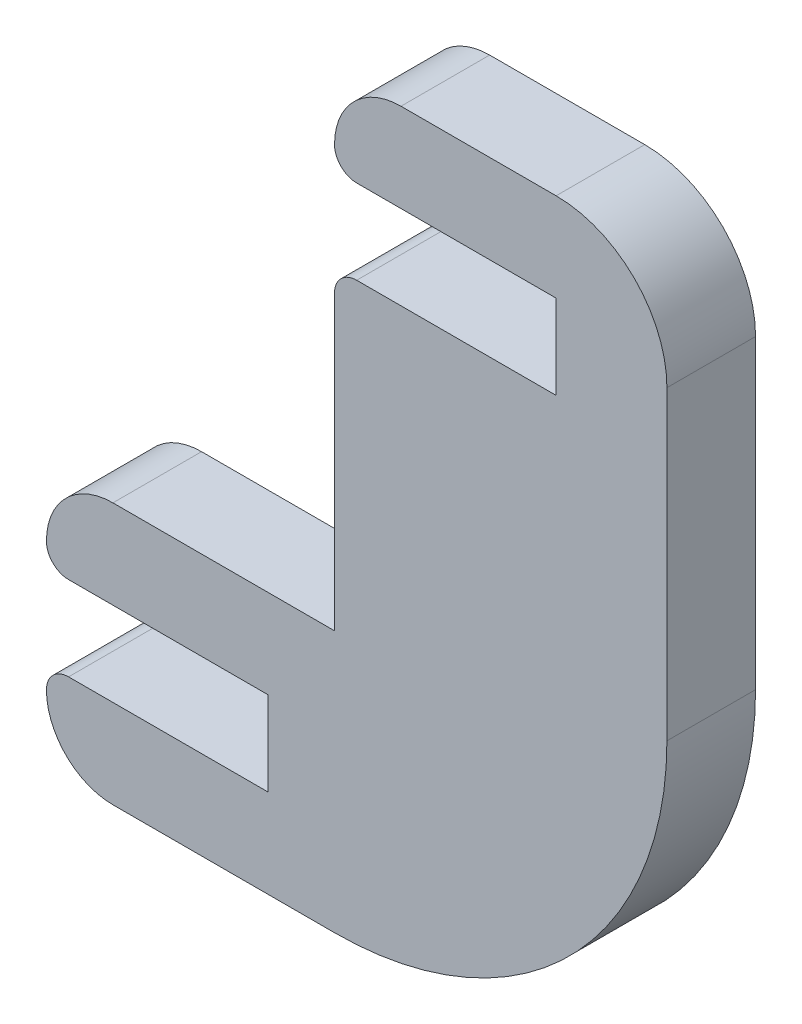
SolidWorks part; units mm, degrees
ref_plane "Piano frontale" through (0, 0, 0) normal (0, 0, 1) x (1, 0, 0)
ref_plane "Piano superiore" through (0, 0, 0) normal (0, 1, 0) x (1, 0, 0)
ref_plane "Piano destro" through (0, 0, 0) normal (1, 0, 0) x (0, 0, -1)
sketch "Schizzo1" plane through (0, 0, 0) normal (0, 0, 1) x (1, 0, 0)
  line L0 (-15, 33.8) -> (0, 33.8)
  line L1 (-15, 33.8) -> (-15, 29.8)
  line L2 (-15, 29.8) -> (-5, 29.8)
  line L3 (-5, 29.8) -> (-5, 26)
  line L4 (-5, 26) -> (-15, 26)
  line L5 (-15, 26) -> (-15, 11.8)
  line L6 (-15, 11.8) -> (-28, 11.8)
  line L7 (-28, 11.8) -> (-28, 7.8)
  line L8 (-28, 7.8) -> (-18, 7.8)
  line L9 (-18, 7.8) -> (-18, 4)
  line L10 (-18, 4) -> (-28, 4)
  line L11 (-28, 4) -> (-28, 0)
  line L12 (-28, 0) -> (0, 0)
  line L13 (0, 33.8) -> (0, 0)
  dimension "D1" = 10
  dimension "D2" = 4
  dimension "D3" = 15
  dimension "D4" = 22
  dimension "D5" = 3.8
  dimension "D6" = 4
  dimension "D7" = 3.8
  dimension "D8" = 10
  dimension "D9" = 4
  dimension "D10" = 13
extrude "Estrusione-Estrusione1" add sketch "Schizzo1" along normal blind 4
fillet "Raccordo1" radius 1 4 edges at (-28, 4, 2) (-28, 7.8, 2) (-15, 26, 2) (-15, 29.8, 2)
fillet "Raccordo2" radius 3 3 edges at (-28, 0, 2) (-28, 11.8, 2) (-15, 33.8, 2)
fillet "Raccordo3" radius 5 1 edges at (0, 33.8, 2)
fillet "Raccordo4" radius 15 1 edges at (0, 0, 2)
